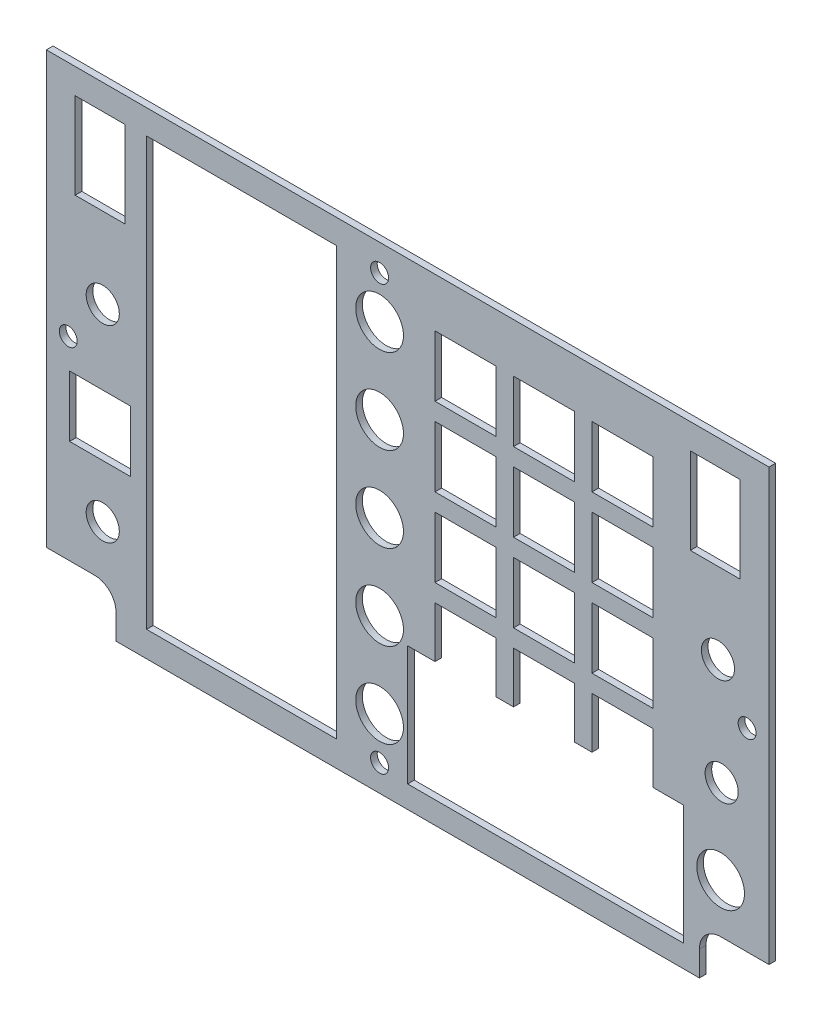
SolidWorks part; units mm, degrees
material "ABS PC"
ref_plane "Front Plane" through (0, 0, 0) normal (0, 0, 1) x (1, 0, 0)
ref_plane "Top Plane" through (0, 0, 0) normal (0, 1, 0) x (1, 0, 0)
ref_plane "Right Plane" through (0, 0, 0) normal (1, 0, 0) x (0, 0, -1)
sketch "Sketch1" plane through (0, 0, 0) normal (0, 0, 1) x (1, 0, 0)
  line L8 (74.93, -171.1167) -> (86.5187, -171.1167)
  line L9 (86.5187, -171.1167) -> (86.5187, -67.9292)
  line L10 (86.5187, -67.9292) -> (-86.5187, -67.9292)
  line L11 (-86.5187, -67.9292) -> (-86.5187, -171.1167)
  line L12 (-86.5187, -171.1167) -> (-74.93, -171.1167)
  line L13 (-69.85, -176.1967) -> (-69.85, -182.2292)
  line L14 (-69.85, -182.2292) -> (69.85, -182.2292)
  line L15 (69.85, -182.2292) -> (69.85, -176.1967)
  line L16 (74.93, -171.1167) -> (86.5187, -171.1167)
  line L17 (86.5187, -171.1167) -> (86.5187, -67.9292)
  line L18 (86.5187, -67.9292) -> (-86.5187, -67.9292)
  line L19 (-86.5187, -67.9292) -> (-86.5187, -171.1167)
  line L20 (-86.5187, -171.1167) -> (-74.93, -171.1167)
  line L21 (-69.85, -176.1967) -> (-69.85, -182.2292)
  line L22 (-69.85, -182.2292) -> (69.85, -182.2292)
  line L23 (69.85, -182.2292) -> (69.85, -176.1967)
  arc A2 (-69.85, -176.1967) -> (-74.93, -171.1167) centre (-74.93, -176.1967) ccw
  arc A3 (74.93, -171.1167) -> (69.85, -176.1967) centre (74.93, -176.1967) ccw
  arc A4 (-69.85, -176.1967) -> (-74.93, -171.1167) centre (-74.93, -176.1967) ccw
  arc A5 (74.93, -171.1167) -> (69.85, -176.1967) centre (74.93, -176.1967) ccw
  dimension "D1" = 0
extrude "Boss-Extrude1" add sketch "Sketch1" against normal blind 1.5875
sketch "Sketch3" plane through (0, 0, 0) normal (0, 0, 1) x (1, 0, 0)
  line L0 (-67.6275, -133.0167) -> (-79.6925, -133.0167) construction
  line L1 (-79.6925, -133.0167) -> (-79.6925, -145.0817) construction
  line L2 (-79.6925, -145.0817) -> (-67.6275, -145.0817) construction
  line L3 (-67.6275, -145.0817) -> (-67.6275, -133.0167) construction
  line L4 (19.8755, -149.3997) -> (19.8755, -137.3347) construction
  line L5 (19.8755, -137.3347) -> (7.8105, -137.3347) construction
  line L6 (7.8105, -137.3347) -> (7.8105, -149.3997) construction
  line L7 (7.8105, -149.3997) -> (19.8755, -149.3997) construction
  line L8 (38.6715, -149.3997) -> (38.6715, -137.3347) construction
  line L9 (38.6715, -137.3347) -> (26.6065, -137.3347) construction
  line L10 (26.6065, -137.3347) -> (26.6065, -149.3997) construction
  line L11 (26.6065, -149.3997) -> (38.6715, -149.3997) construction
  line L12 (45.4025, -149.3997) -> (57.4675, -149.3997) construction
  line L13 (57.4675, -149.3997) -> (57.4675, -137.3347) construction
  line L14 (57.4675, -137.3347) -> (45.4025, -137.3347) construction
  line L15 (45.4025, -137.3347) -> (45.4025, -149.3997) construction
  line L16 (57.4675, -130.6037) -> (57.4675, -118.5387) construction
  line L17 (57.4675, -118.5387) -> (45.4025, -118.5387) construction
  line L18 (45.4025, -118.5387) -> (45.4025, -130.6037) construction
  line L19 (45.4025, -130.6037) -> (57.4675, -130.6037) construction
  line L20 (38.6715, -130.6037) -> (38.6715, -118.5387) construction
  line L21 (38.6715, -118.5387) -> (26.6065, -118.5387) construction
  line L22 (26.6065, -118.5387) -> (26.6065, -130.6037) construction
  line L23 (26.6065, -130.6037) -> (38.6715, -130.6037) construction
  line L24 (19.8755, -130.6037) -> (19.8755, -118.5387) construction
  line L25 (19.8755, -118.5387) -> (7.8105, -118.5387) construction
  line L26 (7.8105, -118.5387) -> (7.8105, -130.6037) construction
  line L27 (7.8105, -130.6037) -> (19.8755, -130.6037) construction
  line L28 (19.8755, -111.8077) -> (19.8755, -99.7427) construction
  line L29 (19.8755, -99.7427) -> (7.8105, -99.7427) construction
  line L30 (7.8105, -99.7427) -> (7.8105, -111.8077) construction
  line L31 (7.8105, -111.8077) -> (19.8755, -111.8077) construction
  line L32 (19.8755, -93.0117) -> (19.8755, -80.9467) construction
  line L33 (19.8755, -80.9467) -> (7.8105, -80.9467) construction
  line L34 (7.8105, -80.9467) -> (7.8105, -93.0117) construction
  line L35 (7.8105, -93.0117) -> (19.8755, -93.0117) construction
  line L36 (38.6715, -93.0117) -> (38.6715, -80.9467) construction
  line L37 (38.6715, -80.9467) -> (26.6065, -80.9467) construction
  line L38 (26.6065, -80.9467) -> (26.6065, -93.0117) construction
  line L39 (26.6065, -93.0117) -> (38.6715, -93.0117) construction
  line L40 (38.6715, -111.8077) -> (38.6715, -99.7427) construction
  line L41 (38.6715, -99.7427) -> (26.6065, -99.7427) construction
  line L42 (26.6065, -99.7427) -> (26.6065, -111.8077) construction
  line L43 (26.6065, -111.8077) -> (38.6715, -111.8077) construction
  line L44 (57.4675, -111.8077) -> (57.4675, -99.7427) construction
  line L45 (57.4675, -99.7427) -> (45.4025, -99.7427) construction
  line L46 (45.4025, -99.7427) -> (45.4025, -111.8077) construction
  line L47 (45.4025, -111.8077) -> (57.4675, -111.8077) construction
  line L48 (57.4675, -93.0117) -> (57.4675, -80.9467) construction
  line L49 (57.4675, -80.9467) -> (45.4025, -80.9467) construction
  line L50 (45.4025, -80.9467) -> (45.4025, -93.0117) construction
  line L51 (45.4025, -93.0117) -> (57.4675, -93.0117) construction
  line L52 (-67.6275, -133.0167) -> (-79.6925, -133.0167)
  line L53 (-79.6925, -133.0167) -> (-79.6925, -145.0817)
  line L54 (-79.6925, -145.0817) -> (-67.6275, -145.0817)
  line L55 (-67.6275, -145.0817) -> (-67.6275, -133.0167)
  line L56 (19.8755, -149.3997) -> (19.8755, -137.3347)
  line L57 (19.8755, -137.3347) -> (7.8105, -137.3347)
  line L58 (7.8105, -137.3347) -> (7.8105, -149.3997)
  line L59 (7.8105, -149.3997) -> (19.8755, -149.3997)
  line L60 (38.6715, -149.3997) -> (38.6715, -137.3347)
  line L61 (38.6715, -137.3347) -> (26.6065, -137.3347)
  line L62 (26.6065, -137.3347) -> (26.6065, -149.3997)
  line L63 (26.6065, -149.3997) -> (38.6715, -149.3997)
  line L64 (45.4025, -149.3997) -> (57.4675, -149.3997)
  line L65 (57.4675, -149.3997) -> (57.4675, -137.3347)
  line L66 (57.4675, -137.3347) -> (45.4025, -137.3347)
  line L67 (45.4025, -137.3347) -> (45.4025, -149.3997)
  line L68 (57.4675, -130.6037) -> (57.4675, -118.5387)
  line L69 (57.4675, -118.5387) -> (45.4025, -118.5387)
  line L70 (45.4025, -118.5387) -> (45.4025, -130.6037)
  line L71 (45.4025, -130.6037) -> (57.4675, -130.6037)
  line L72 (38.6715, -130.6037) -> (38.6715, -118.5387)
  line L73 (38.6715, -118.5387) -> (26.6065, -118.5387)
  line L74 (26.6065, -118.5387) -> (26.6065, -130.6037)
  line L75 (26.6065, -130.6037) -> (38.6715, -130.6037)
  line L76 (19.8755, -130.6037) -> (19.8755, -118.5387)
  line L77 (19.8755, -118.5387) -> (7.8105, -118.5387)
  line L78 (7.8105, -118.5387) -> (7.8105, -130.6037)
  line L79 (7.8105, -130.6037) -> (19.8755, -130.6037)
  line L80 (19.8755, -111.8077) -> (19.8755, -99.7427)
  line L81 (19.8755, -99.7427) -> (7.8105, -99.7427)
  line L82 (7.8105, -99.7427) -> (7.8105, -111.8077)
  line L83 (7.8105, -111.8077) -> (19.8755, -111.8077)
  line L84 (19.8755, -93.0117) -> (19.8755, -80.9467)
  line L85 (19.8755, -80.9467) -> (7.8105, -80.9467)
  line L86 (7.8105, -80.9467) -> (7.8105, -93.0117)
  line L87 (7.8105, -93.0117) -> (19.8755, -93.0117)
  line L88 (38.6715, -93.0117) -> (38.6715, -80.9467)
  line L89 (38.6715, -80.9467) -> (26.6065, -80.9467)
  line L90 (26.6065, -80.9467) -> (26.6065, -93.0117)
  line L91 (26.6065, -93.0117) -> (38.6715, -93.0117)
  line L92 (38.6715, -111.8077) -> (38.6715, -99.7427)
  line L93 (38.6715, -99.7427) -> (26.6065, -99.7427)
  line L94 (26.6065, -99.7427) -> (26.6065, -111.8077)
  line L95 (26.6065, -111.8077) -> (38.6715, -111.8077)
  line L96 (57.4675, -111.8077) -> (57.4675, -99.7427)
  line L97 (57.4675, -99.7427) -> (45.4025, -99.7427)
  line L98 (45.4025, -99.7427) -> (45.4025, -111.8077)
  line L99 (45.4025, -111.8077) -> (57.4675, -111.8077)
  line L100 (57.4675, -93.0117) -> (57.4675, -80.9467)
  line L101 (57.4675, -80.9467) -> (45.4025, -80.9467)
  line L102 (45.4025, -80.9467) -> (45.4025, -93.0117)
  line L103 (45.4025, -93.0117) -> (57.4675, -93.0117)
  circle A0 centre (74.93, -159.3692) radius 4.445 construction
  circle A1 centre (-6.731, -165.7192) radius 4.445 construction
  circle A2 centre (-6.731, -145.3992) radius 4.445 construction
  circle A3 centre (-6.731, -125.0792) radius 4.445 construction
  circle A4 centre (-6.731, -104.7592) radius 4.445 construction
  circle A5 centre (-6.731, -84.4392) radius 4.445 construction
  circle A6 centre (74.93, -159.3692) radius 4.445
  circle A7 centre (-6.731, -165.7192) radius 4.445
  circle A8 centre (-6.731, -145.3992) radius 4.445
  circle A9 centre (-6.731, -125.0792) radius 4.445
  circle A10 centre (-6.731, -104.7592) radius 4.445
  circle A11 centre (-6.731, -84.4392) radius 4.445
extrude "Cut-Extrude1" cut sketch "Sketch3" against normal through all
sketch "Sketch4" plane through (0, 0, 0) normal (0, 0, 1) x (1, 0, 0)
  circle A0 centre (-73.025, -113.9667) radius 3.9688
  circle A1 centre (-73.025, -159.0517) radius 3.9688
  circle A2 centre (74.295, -113.9667) radius 3.9688
  circle A3 centre (75.184, -139.0492) radius 3.9687
  dimension "D1" = 7.9375
extrude "Cut-Extrude2" cut sketch "Sketch4" against normal through all
sketch "Sketch5" plane through (0, 0, 0) normal (0, 0, 1) x (1, 0, 0)
  line L0 (-79.63, -73.9922) -> (-79.63, -94.6322)
  line L1 (-79.63, -94.6322) -> (-67.69, -94.6322)
  line L2 (-67.69, -94.6322) -> (-67.69, -73.9922)
  line L3 (-67.69, -73.9922) -> (-79.63, -73.9922)
  line L4 (-78.36, -75.2622) -> (-78.36, -93.3622)
  line L5 (-78.36, -93.3622) -> (-68.96, -93.3622)
  line L6 (-68.96, -93.3622) -> (-68.96, -75.2622)
  line L7 (-68.96, -75.2622) -> (-78.36, -75.2622)
  line L8 (-78.36, -75.2622) -> (-78.36, -93.3622) construction
  line L9 (-78.36, -93.3622) -> (-68.96, -93.3622) construction
  line L10 (-68.96, -93.3622) -> (-68.96, -75.2622) construction
  line L11 (-68.96, -75.2622) -> (-78.36, -75.2622) construction
  line L12 (68.96, -75.2622) -> (68.96, -93.3622)
  line L13 (68.96, -93.3622) -> (78.36, -93.3622)
  line L14 (78.36, -93.3622) -> (78.36, -75.2622)
  line L15 (78.36, -75.2622) -> (68.96, -75.2622)
  line L16 (68.96, -75.2622) -> (68.96, -93.3622) construction
  line L17 (68.96, -93.3622) -> (78.36, -93.3622) construction
  line L18 (78.36, -93.3622) -> (78.36, -75.2622) construction
  line L19 (78.36, -75.2622) -> (68.96, -75.2622) construction
  line L20 (67.69, -73.9922) -> (67.69, -94.6322)
  line L21 (67.69, -94.6322) -> (79.63, -94.6322)
  line L22 (79.63, -94.6322) -> (79.63, -73.9922)
  line L23 (79.63, -73.9922) -> (67.69, -73.9922)
  line L24 (-61.06, -75.0622) -> (-51.66, -75.0622) construction
  line L25 (-62.53, -73.7922) -> (-17.068, -73.7922)
  line L26 (-62.53, -73.7922) -> (-62.53, -176.1122)
  line L27 (-62.53, -176.1122) -> (-17.068, -176.1122)
  line L28 (-17.068, -73.7922) -> (-17.068, -176.1122)
  line L29 (-62.53, -73.7922) -> (-17.068, -176.1122) construction
  line L30 (-62.53, -176.1122) -> (-17.068, -73.7922) construction
  line L31 (-61.26, -93.3622) -> (-61.26, -75.2622) construction
  line L32 (-51.66, -174.8422) -> (-61.06, -174.8422) construction
  line L33 (-18.338, -167.7344) -> (-18.338, -169.4031) construction
  line L34 (61.52, -158.4422) -> (61.52, -172.5422) construction
  line L35 (5.02, -157.9422) -> (61.02, -157.9422) construction
  line L36 (61.02, -173.0422) -> (5.02, -173.0422) construction
  line L37 (4.52, -172.5422) -> (4.52, -158.4422) construction
  line L38 (61.52, -157.9422) -> (61.52, -173.0422)
  line L39 (4.52, -157.9422) -> (61.52, -157.9422)
  line L40 (61.52, -173.0422) -> (4.52, -173.0422)
  line L41 (4.52, -173.0422) -> (4.52, -157.9422)
  point P20 (-39.799, -124.9522)
  dimension "D4" = 1.27
  dimension "D5" = 1.27
  dimension "D6" = 1.27
  dimension "D7" = 1.27
  dimension "D1" = 0
  dimension "D2" = 0
  dimension "D3" = 1.27
extrude "Cut-Extrude3" cut sketch "Sketch5" against normal through all
sketch "Sketch6" plane through (0, 0, 0) normal (0, 0, 1) x (1, 0, 0)
  line L4 (-67.6275, -133.0167) -> (-79.6925, -133.0167) construction
  line L5 (57.4675, -137.3347) -> (45.4025, -137.3347) construction
  line L6 (45.4025, -137.3347) -> (45.4025, -149.3997) construction
  line L7 (45.4025, -149.3997) -> (57.4675, -149.3997) construction
  line L8 (57.4675, -149.3997) -> (57.4675, -137.3347) construction
  line L9 (45.4025, -130.6037) -> (57.4675, -130.6037) construction
  line L10 (57.4675, -130.6037) -> (57.4675, -118.5387) construction
  line L11 (57.4675, -118.5387) -> (45.4025, -118.5387) construction
  line L12 (45.4025, -118.5387) -> (45.4025, -130.6037) construction
  line L13 (45.4025, -111.8077) -> (57.4675, -111.8077) construction
  line L14 (57.4675, -111.8077) -> (57.4675, -99.7427) construction
  line L15 (57.4675, -99.7427) -> (45.4025, -99.7427) construction
  line L16 (45.4025, -99.7427) -> (45.4025, -111.8077) construction
  line L17 (45.4025, -93.0117) -> (57.4675, -93.0117) construction
  line L18 (57.4675, -93.0117) -> (57.4675, -80.9467) construction
  line L19 (57.4675, -80.9467) -> (45.4025, -80.9467) construction
  line L20 (45.4025, -80.9467) -> (45.4025, -93.0117) construction
  line L21 (26.6065, -149.3997) -> (38.6715, -149.3997) construction
  line L22 (38.6715, -149.3997) -> (38.6715, -137.3347) construction
  line L23 (38.6715, -137.3347) -> (26.6065, -137.3347) construction
  line L24 (26.6065, -137.3347) -> (26.6065, -149.3997) construction
  line L25 (26.6065, -130.6037) -> (38.6715, -130.6037) construction
  line L26 (38.6715, -130.6037) -> (38.6715, -118.5387) construction
  line L27 (38.6715, -118.5387) -> (26.6065, -118.5387) construction
  line L28 (26.6065, -118.5387) -> (26.6065, -130.6037) construction
  line L29 (26.6065, -111.8077) -> (38.6715, -111.8077) construction
  line L30 (38.6715, -111.8077) -> (38.6715, -99.7427) construction
  line L31 (38.6715, -99.7427) -> (26.6065, -99.7427) construction
  line L32 (26.6065, -99.7427) -> (26.6065, -111.8077) construction
  line L33 (26.6065, -93.0117) -> (38.6715, -93.0117) construction
  line L34 (38.6715, -93.0117) -> (38.6715, -80.9467) construction
  line L35 (38.6715, -80.9467) -> (26.6065, -80.9467) construction
  line L36 (26.6065, -80.9467) -> (26.6065, -93.0117) construction
  line L37 (7.8105, -93.0117) -> (19.8755, -93.0117) construction
  line L38 (19.8755, -93.0117) -> (19.8755, -80.9467) construction
  line L39 (19.8755, -80.9467) -> (7.8105, -80.9467) construction
  line L40 (7.8105, -80.9467) -> (7.8105, -93.0117) construction
  line L41 (7.8105, -111.8077) -> (19.8755, -111.8077) construction
  line L42 (19.8755, -111.8077) -> (19.8755, -99.7427) construction
  line L43 (19.8755, -99.7427) -> (7.8105, -99.7427) construction
  line L44 (7.8105, -99.7427) -> (7.8105, -111.8077) construction
  line L45 (19.8755, -118.5387) -> (7.8105, -118.5387) construction
  line L46 (7.8105, -118.5387) -> (7.8105, -130.6037) construction
  line L47 (7.8105, -130.6037) -> (19.8755, -130.6037) construction
  line L48 (19.8755, -130.6037) -> (19.8755, -118.5387) construction
  line L49 (19.8755, -137.3347) -> (7.8105, -137.3347) construction
  line L50 (7.8105, -137.3347) -> (7.8105, -149.3997) construction
  line L51 (7.8105, -149.3997) -> (19.8755, -149.3997) construction
  line L52 (19.8755, -149.3997) -> (19.8755, -137.3347) construction
  line L53 (-79.6925, -133.0167) -> (-79.6925, -145.0817) construction
  line L54 (-79.6925, -145.0817) -> (-67.6275, -145.0817) construction
  line L55 (-67.6275, -145.0817) -> (-67.6275, -133.0167) construction
  line L56 (57.4675, -137.3347) -> (45.4025, -137.3347) construction
  line L57 (45.4025, -137.3347) -> (45.4025, -149.3997) construction
  line L58 (45.4025, -149.3997) -> (57.4675, -149.3997) construction
  line L59 (57.4675, -149.3997) -> (57.4675, -137.3347) construction
  line L60 (45.4025, -130.6037) -> (57.4675, -130.6037) construction
  line L61 (57.4675, -130.6037) -> (57.4675, -118.5387) construction
  line L62 (57.4675, -118.5387) -> (45.4025, -118.5387) construction
  line L63 (45.4025, -118.5387) -> (45.4025, -130.6037) construction
  line L64 (45.4025, -111.8077) -> (57.4675, -111.8077) construction
  line L65 (57.4675, -111.8077) -> (57.4675, -99.7427) construction
  line L66 (57.4675, -99.7427) -> (45.4025, -99.7427) construction
  line L67 (45.4025, -99.7427) -> (45.4025, -111.8077) construction
  line L68 (45.4025, -93.0117) -> (57.4675, -93.0117) construction
  line L69 (57.4675, -93.0117) -> (57.4675, -80.9467) construction
  line L70 (57.4675, -80.9467) -> (45.4025, -80.9467) construction
  line L71 (45.4025, -80.9467) -> (45.4025, -93.0117) construction
  line L72 (26.6065, -149.3997) -> (38.6715, -149.3997) construction
  line L73 (38.6715, -149.3997) -> (38.6715, -137.3347) construction
  line L74 (38.6715, -137.3347) -> (26.6065, -137.3347) construction
  line L75 (26.6065, -137.3347) -> (26.6065, -149.3997) construction
  line L76 (26.6065, -130.6037) -> (38.6715, -130.6037) construction
  line L77 (38.6715, -130.6037) -> (38.6715, -118.5387) construction
  line L78 (38.6715, -118.5387) -> (26.6065, -118.5387) construction
  line L79 (26.6065, -118.5387) -> (26.6065, -130.6037) construction
  line L80 (26.6065, -111.8077) -> (38.6715, -111.8077) construction
  line L81 (38.6715, -111.8077) -> (38.6715, -99.7427) construction
  line L82 (38.6715, -99.7427) -> (26.6065, -99.7427) construction
  line L83 (26.6065, -99.7427) -> (26.6065, -111.8077) construction
  line L84 (26.6065, -93.0117) -> (38.6715, -93.0117) construction
  line L85 (38.6715, -93.0117) -> (38.6715, -80.9467) construction
  line L86 (38.6715, -80.9467) -> (26.6065, -80.9467) construction
  line L87 (26.6065, -80.9467) -> (26.6065, -93.0117) construction
  line L88 (7.8105, -93.0117) -> (19.8755, -93.0117) construction
  line L89 (19.8755, -93.0117) -> (19.8755, -80.9467) construction
  line L90 (19.8755, -80.9467) -> (7.8105, -80.9467) construction
  line L91 (7.8105, -80.9467) -> (7.8105, -93.0117) construction
  line L92 (7.8105, -111.8077) -> (19.8755, -111.8077) construction
  line L93 (19.8755, -111.8077) -> (19.8755, -99.7427) construction
  line L94 (19.8755, -99.7427) -> (7.8105, -99.7427) construction
  line L95 (7.8105, -99.7427) -> (7.8105, -111.8077) construction
  line L96 (19.8755, -118.5387) -> (7.8105, -118.5387) construction
  line L97 (7.8105, -118.5387) -> (7.8105, -130.6037) construction
  line L98 (7.8105, -130.6037) -> (19.8755, -130.6037) construction
  line L99 (19.8755, -130.6037) -> (19.8755, -118.5387) construction
  line L100 (19.8755, -137.3347) -> (7.8105, -137.3347) construction
  line L101 (7.8105, -137.3347) -> (7.8105, -149.3997) construction
  line L102 (7.8105, -149.3997) -> (19.8755, -149.3997) construction
  line L103 (19.8755, -149.3997) -> (19.8755, -137.3347) construction
  line L104 (-67.6275, -133.0167) -> (-79.6925, -133.0167) construction
  line L105 (-79.6925, -133.0167) -> (-79.6925, -145.0817) construction
  line L106 (-79.6925, -145.0817) -> (-67.6275, -145.0817) construction
  line L107 (-67.6275, -145.0817) -> (-67.6275, -133.0167) construction
  line L108 (58.7375, -136.0647) -> (44.1325, -136.0647)
  line L109 (44.1325, -136.0647) -> (44.1325, -150.6697)
  line L110 (44.1325, -150.6697) -> (58.7375, -150.6697)
  line L111 (58.7375, -150.6697) -> (58.7375, -136.0647)
  line L112 (44.1325, -131.8737) -> (58.7375, -131.8737)
  line L113 (58.7375, -131.8737) -> (58.7375, -117.2687)
  line L114 (58.7375, -117.2687) -> (44.1325, -117.2687)
  line L115 (44.1325, -117.2687) -> (44.1325, -131.8737)
  line L116 (44.1325, -113.0777) -> (58.7375, -113.0777)
  line L117 (58.7375, -113.0777) -> (58.7375, -98.4727)
  line L118 (58.7375, -98.4727) -> (44.1325, -98.4727)
  line L119 (44.1325, -98.4727) -> (44.1325, -113.0777)
  line L120 (44.1325, -94.2817) -> (58.7375, -94.2817)
  line L121 (58.7375, -94.2817) -> (58.7375, -79.6767)
  line L122 (58.7375, -79.6767) -> (44.1325, -79.6767)
  line L123 (44.1325, -79.6767) -> (44.1325, -94.2817)
  line L124 (25.3365, -150.6697) -> (39.9415, -150.6697)
  line L125 (39.9415, -150.6697) -> (39.9415, -136.0647)
  line L126 (39.9415, -136.0647) -> (25.3365, -136.0647)
  line L127 (25.3365, -136.0647) -> (25.3365, -150.6697)
  line L128 (25.3365, -131.8737) -> (39.9415, -131.8737)
  line L129 (39.9415, -131.8737) -> (39.9415, -117.2687)
  line L130 (39.9415, -117.2687) -> (25.3365, -117.2687)
  line L131 (25.3365, -117.2687) -> (25.3365, -131.8737)
  line L132 (25.3365, -113.0777) -> (39.9415, -113.0777)
  line L133 (39.9415, -113.0777) -> (39.9415, -98.4727)
  line L134 (39.9415, -98.4727) -> (25.3365, -98.4727)
  line L135 (25.3365, -98.4727) -> (25.3365, -113.0777)
  line L136 (25.3365, -94.2817) -> (39.9415, -94.2817)
  line L137 (39.9415, -94.2817) -> (39.9415, -79.6767)
  line L138 (39.9415, -79.6767) -> (25.3365, -79.6767)
  line L139 (25.3365, -79.6767) -> (25.3365, -94.2817)
  line L140 (6.5405, -94.2817) -> (21.1455, -94.2817)
  line L141 (21.1455, -94.2817) -> (21.1455, -79.6767)
  line L142 (21.1455, -79.6767) -> (6.5405, -79.6767)
  line L143 (6.5405, -79.6767) -> (6.5405, -94.2817)
  line L144 (6.5405, -113.0777) -> (21.1455, -113.0777)
  line L145 (21.1455, -113.0777) -> (21.1455, -98.4727)
  line L146 (21.1455, -98.4727) -> (6.5405, -98.4727)
  line L147 (6.5405, -98.4727) -> (6.5405, -113.0777)
  line L148 (21.1455, -117.2687) -> (6.5405, -117.2687)
  line L149 (6.5405, -117.2687) -> (6.5405, -131.8737)
  line L150 (6.5405, -131.8737) -> (21.1455, -131.8737)
  line L151 (21.1455, -131.8737) -> (21.1455, -117.2687)
  line L152 (21.1455, -136.0647) -> (6.5405, -136.0647)
  line L153 (6.5405, -136.0647) -> (6.5405, -150.6697)
  line L154 (6.5405, -150.6697) -> (21.1455, -150.6697)
  line L155 (21.1455, -150.6697) -> (21.1455, -136.0647)
  line L156 (-66.3575, -131.7467) -> (-80.9625, -131.7467)
  line L157 (-80.9625, -131.7467) -> (-80.9625, -146.3517)
  line L158 (-80.9625, -146.3517) -> (-66.3575, -146.3517)
  line L159 (-66.3575, -146.3517) -> (-66.3575, -131.7467)
  circle A6 centre (74.93, -159.3692) radius 4.445 construction
  circle A7 centre (-6.731, -165.7192) radius 4.445 construction
  circle A9 centre (-6.731, -145.3992) radius 4.445 construction
  circle A12 centre (-6.731, -125.0792) radius 4.445 construction
  circle A16 centre (-6.731, -104.7592) radius 4.445 construction
  circle A21 centre (-6.731, -84.4392) radius 4.445 construction
  circle A33 centre (74.93, -159.3692) radius 4.445 construction
  circle A34 centre (-6.731, -165.7192) radius 4.445 construction
  circle A35 centre (-6.731, -145.3992) radius 4.445 construction
  circle A36 centre (-6.731, -125.0792) radius 4.445 construction
  circle A37 centre (-6.731, -104.7592) radius 4.445 construction
  circle A38 centre (-6.731, -84.4392) radius 4.445 construction
  circle A39 centre (74.93, -159.3692) radius 5.715
  circle A40 centre (-6.731, -165.7192) radius 5.715
  circle A41 centre (-6.731, -145.3992) radius 5.715
  circle A42 centre (-6.731, -125.0792) radius 5.715
  circle A43 centre (-6.731, -104.7592) radius 5.715
  circle A44 centre (-6.731, -84.4392) radius 5.715
  dimension "D1" = 1.27
extrude "Cut-Extrude4" cut sketch "Sketch6" against normal through all
sketch "Sketch7" plane through (0, 0, 0) normal (0, 0, 1) x (1, 0, 0)
  line L0 (66.04, -176.9122) -> (66.04, -148.2722)
  line L1 (66.04, -148.2722) -> (0, -148.2722)
  line L2 (0, -148.2722) -> (0, -176.9122)
  line L3 (0, -176.9122) -> (66.04, -176.9122)
  line L4 (64.77, -175.6422) -> (64.77, -149.5422)
  line L5 (64.77, -149.5422) -> (1.27, -149.5422)
  line L6 (1.27, -149.5422) -> (1.27, -175.6422)
  line L7 (1.27, -175.6422) -> (64.77, -175.6422)
  line L8 (64.77, -175.6422) -> (64.77, -149.5422) construction
  line L9 (64.77, -149.5422) -> (1.27, -149.5422) construction
  line L10 (1.27, -149.5422) -> (1.27, -175.6422) construction
  line L11 (1.27, -175.6422) -> (64.77, -175.6422) construction
  dimension "D1" = 0
  dimension "D2" = 1.27
extrude "Cut-Extrude5" cut sketch "Sketch7" against normal through all
hole_wizard "#6 Clearance Hole2" positions "Sketch10" profile "Sketch11" hole size "#6" standard "ANSI Inch" end condition through all
sketch "Sketch10" plane through (0, 0, 1.5875) normal (0, 0, 1) x (-1, 0, 0)
  point P0 (-81.28, 124.6982)
  point P3 (6.731, 175.8792)
  point P6 (81.28, 124.6982)
  point P9 (6.731, 74.2792)
sketch "Sketch11" plane through (81.28, -124.6982, 1.5875) normal (1, 0, 0) x (0, -1, 0)
  line L0 (0, 0) -> (0, 3.175)
  line L1 (0, 3.175) -> (2.1526, 3.175)
  line L2 (2.1526, 3.175) -> (2.1526, 0)
  line L3 (2.1526, 0) -> (0, 0)
  line L4 (0, -6.35) -> (0, 107.95) construction
  dimension "Thru Hole Dia." = 4.3053
  dimension "Thru Hole Depth" = 3.175
